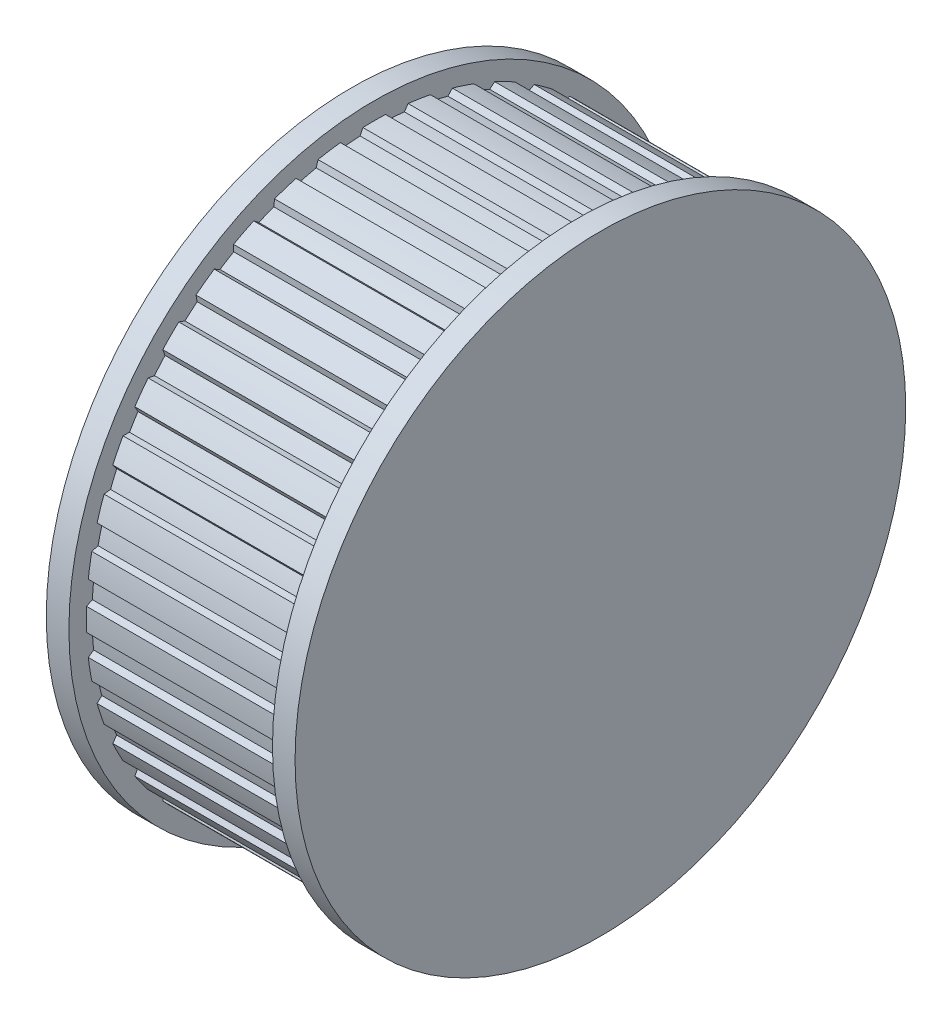
SolidWorks part; units mm, degrees
ref_plane "Front Plane" through (0, 0, 0) normal (0, 0, 1) x (1, 0, 0)
ref_plane "Top Plane" through (0, 0, 0) normal (0, 1, 0) x (1, 0, 0)
ref_plane "Right Plane" through (0, 0, 0) normal (1, 0, 0) x (0, 0, -1)
ref_plane "Plane4" through (0, 0, 0) normal (0, 0, -1) x (-1, 0, 0)
sketch "Sketch5" plane through (0, 0, 0) normal (1, 0, 0) x (0, 0, -1)
  line L1 (0, 12.73) -> (0, 0) construction
  line L2 (-0.6228, 12.4594) -> (-0.4998, 12.7202)
  line L3 (0.4998, 12.7202) -> (0.6228, 12.4594)
  line L4 (1.3339, 12.4035) -> (1.4963, 12.6418)
  line L5 (2.4835, 12.4854) -> (2.5642, 12.2086)
  line L6 (3.2578, 12.0421) -> (3.4554, 12.2521)
  line L7 (4.4061, 11.9432) -> (4.4425, 11.6572)
  line L8 (5.1015, 11.3842) -> (5.3295, 11.5607)
  line L9 (6.2201, 11.1069) -> (6.2114, 10.8187)
  line L10 (6.8196, 10.446) -> (7.0724, 10.5846)
  line L11 (7.8811, 9.9971) -> (7.8273, 9.7138)
  line L12 (8.3698, 9.2506) -> (8.6411, 9.3479)
  line L13 (9.3479, 8.6411) -> (9.2506, 8.3698)
  line L14 (9.7138, 7.8273) -> (9.9971, 7.8811)
  line L15 (10.5846, 7.0724) -> (10.446, 6.8196)
  line L16 (10.8187, 6.2114) -> (11.1069, 6.2201)
  line L17 (11.5607, 5.3295) -> (11.3842, 5.1015)
  line L18 (11.6572, 4.4425) -> (11.9432, 4.4061)
  line L19 (12.2521, 3.4554) -> (12.0421, 3.2578)
  line L20 (12.2086, 2.5642) -> (12.4854, 2.4835)
  line L21 (12.6418, 1.4963) -> (12.4035, 1.3339)
  line L22 (12.4594, 0.6228) -> (12.7202, 0.4998)
  line L23 (12.7202, -0.4998) -> (12.4594, -0.6228)
  line L24 (12.4035, -1.3339) -> (12.6418, -1.4963)
  line L25 (12.4854, -2.4835) -> (12.2086, -2.5642)
  line L26 (12.0421, -3.2578) -> (12.2521, -3.4554)
  line L27 (11.9432, -4.4061) -> (11.6572, -4.4425)
  line L28 (11.3842, -5.1015) -> (11.5607, -5.3295)
  line L29 (11.1069, -6.2201) -> (10.8187, -6.2114)
  line L30 (10.446, -6.8196) -> (10.5846, -7.0724)
  line L31 (9.9971, -7.8811) -> (9.7138, -7.8273)
  line L32 (9.2506, -8.3698) -> (9.3479, -8.6411)
  line L33 (8.6411, -9.3479) -> (8.3698, -9.2506)
  line L34 (7.8273, -9.7138) -> (7.8811, -9.9971)
  line L35 (7.0724, -10.5846) -> (6.8196, -10.446)
  line L36 (6.2114, -10.8187) -> (6.2201, -11.1069)
  line L37 (5.3295, -11.5607) -> (5.1015, -11.3842)
  line L38 (4.4425, -11.6572) -> (4.4061, -11.9432)
  line L39 (3.4554, -12.2521) -> (3.2578, -12.0421)
  line L40 (2.5642, -12.2086) -> (2.4835, -12.4854)
  line L41 (1.4963, -12.6418) -> (1.3339, -12.4035)
  line L42 (0.6228, -12.4594) -> (0.4998, -12.7202)
  line L43 (-0.4998, -12.7202) -> (-0.6228, -12.4594)
  line L44 (-1.3339, -12.4035) -> (-1.4963, -12.6418)
  line L45 (-2.4835, -12.4854) -> (-2.5642, -12.2086)
  line L46 (-3.2578, -12.0421) -> (-3.4554, -12.2521)
  line L47 (-4.4061, -11.9432) -> (-4.4425, -11.6572)
  line L48 (-5.1015, -11.3842) -> (-5.3295, -11.5607)
  line L49 (-6.2201, -11.1069) -> (-6.2114, -10.8187)
  line L50 (-6.8196, -10.446) -> (-7.0724, -10.5846)
  line L51 (-7.8811, -9.9971) -> (-7.8273, -9.7138)
  line L52 (-8.3698, -9.2506) -> (-8.6411, -9.3479)
  line L53 (-9.3479, -8.6411) -> (-9.2506, -8.3698)
  line L54 (-9.7138, -7.8273) -> (-9.9971, -7.8811)
  line L55 (-10.5846, -7.0724) -> (-10.446, -6.8196)
  line L56 (-10.8187, -6.2114) -> (-11.1069, -6.2201)
  line L57 (-11.5607, -5.3295) -> (-11.3842, -5.1015)
  line L58 (-11.6572, -4.4425) -> (-11.9432, -4.4061)
  line L59 (-12.2521, -3.4554) -> (-12.0421, -3.2578)
  line L60 (-12.2086, -2.5642) -> (-12.4854, -2.4835)
  line L61 (-12.6418, -1.4963) -> (-12.4035, -1.3339)
  line L62 (-12.4594, -0.6228) -> (-12.7202, -0.4998)
  line L63 (-12.7202, 0.4998) -> (-12.4594, 0.6228)
  line L64 (-12.4035, 1.3339) -> (-12.6418, 1.4963)
  line L65 (-12.4854, 2.4835) -> (-12.2086, 2.5642)
  line L66 (-12.0421, 3.2578) -> (-12.2521, 3.4554)
  line L67 (-11.9432, 4.4061) -> (-11.6572, 4.4425)
  line L68 (-11.3842, 5.1015) -> (-11.5607, 5.3295)
  line L69 (-11.1069, 6.2201) -> (-10.8187, 6.2114)
  line L70 (-10.446, 6.8196) -> (-10.5846, 7.0724)
  line L71 (-9.9971, 7.8811) -> (-9.7138, 7.8273)
  line L72 (-9.2506, 8.3698) -> (-9.3479, 8.6411)
  line L73 (-8.6411, 9.3479) -> (-8.3698, 9.2506)
  line L74 (-7.8273, 9.7138) -> (-7.8811, 9.9971)
  line L75 (-7.0724, 10.5846) -> (-6.8196, 10.446)
  line L76 (-6.2114, 10.8187) -> (-6.2201, 11.1069)
  line L77 (-5.3295, 11.5607) -> (-5.1015, 11.3842)
  line L78 (-4.4425, 11.6572) -> (-4.4061, 11.9432)
  line L79 (-3.4554, 12.2521) -> (-3.2578, 12.0421)
  line L80 (-2.5642, 12.2086) -> (-2.4835, 12.4854)
  line L81 (-1.4963, 12.6418) -> (-1.3339, 12.4035)
  arc A4 (1.3339, 12.4035) -> (0.6228, 12.4594) centre (0, 0) ccw
  arc A6 (0.4998, 12.7202) -> (-0.4998, 12.7202) centre (0, 0) ccw
  arc A7 (2.4835, 12.4854) -> (1.4963, 12.6418) centre (0, 0) ccw
  arc A8 (3.2578, 12.0421) -> (2.5642, 12.2086) centre (0, 0) ccw
  arc A9 (4.4061, 11.9432) -> (3.4554, 12.2521) centre (0, 0) ccw
  arc A10 (5.1015, 11.3842) -> (4.4425, 11.6572) centre (0, 0) ccw
  arc A11 (6.2201, 11.1069) -> (5.3295, 11.5607) centre (0, 0) ccw
  arc A12 (6.8196, 10.446) -> (6.2114, 10.8187) centre (0, 0) ccw
  arc A13 (7.8811, 9.9971) -> (7.0724, 10.5846) centre (0, 0) ccw
  arc A14 (8.3698, 9.2506) -> (7.8273, 9.7138) centre (0, 0) ccw
  arc A15 (9.3479, 8.6411) -> (8.6411, 9.3479) centre (0, 0) ccw
  arc A16 (9.7138, 7.8273) -> (9.2506, 8.3698) centre (0, 0) ccw
  arc A17 (10.5846, 7.0724) -> (9.9971, 7.8811) centre (0, 0) ccw
  arc A18 (10.8187, 6.2114) -> (10.446, 6.8196) centre (0, 0) ccw
  arc A19 (11.5607, 5.3295) -> (11.1069, 6.2201) centre (0, 0) ccw
  arc A20 (11.6572, 4.4425) -> (11.3842, 5.1015) centre (0, 0) ccw
  arc A21 (12.2521, 3.4554) -> (11.9432, 4.4061) centre (0, 0) ccw
  arc A22 (12.2086, 2.5642) -> (12.0421, 3.2578) centre (0, 0) ccw
  arc A23 (12.6418, 1.4963) -> (12.4854, 2.4835) centre (0, 0) ccw
  arc A24 (12.4594, 0.6228) -> (12.4035, 1.3339) centre (0, 0) ccw
  arc A25 (12.7202, -0.4998) -> (12.7202, 0.4998) centre (0, 0) ccw
  arc A26 (12.4035, -1.3339) -> (12.4594, -0.6228) centre (0, 0) ccw
  arc A27 (12.4854, -2.4835) -> (12.6418, -1.4963) centre (0, 0) ccw
  arc A28 (12.0421, -3.2578) -> (12.2086, -2.5642) centre (0, 0) ccw
  arc A29 (11.9432, -4.4061) -> (12.2521, -3.4554) centre (0, 0) ccw
  arc A30 (11.3842, -5.1015) -> (11.6572, -4.4425) centre (0, 0) ccw
  arc A31 (11.1069, -6.2201) -> (11.5607, -5.3295) centre (0, 0) ccw
  arc A32 (10.446, -6.8196) -> (10.8187, -6.2114) centre (0, 0) ccw
  arc A33 (9.9971, -7.8811) -> (10.5846, -7.0724) centre (0, 0) ccw
  arc A34 (9.2506, -8.3698) -> (9.7138, -7.8273) centre (0, 0) ccw
  arc A35 (8.6411, -9.3479) -> (9.3479, -8.6411) centre (0, 0) ccw
  arc A36 (7.8273, -9.7138) -> (8.3698, -9.2506) centre (0, 0) ccw
  arc A37 (7.0724, -10.5846) -> (7.8811, -9.9971) centre (0, 0) ccw
  arc A38 (6.2114, -10.8187) -> (6.8196, -10.446) centre (0, 0) ccw
  arc A39 (5.3295, -11.5607) -> (6.2201, -11.1069) centre (0, 0) ccw
  arc A40 (4.4425, -11.6572) -> (5.1015, -11.3842) centre (0, 0) ccw
  arc A41 (3.4554, -12.2521) -> (4.4061, -11.9432) centre (0, 0) ccw
  arc A42 (2.5642, -12.2086) -> (3.2578, -12.0421) centre (0, 0) ccw
  arc A43 (1.4963, -12.6418) -> (2.4835, -12.4854) centre (0, 0) ccw
  arc A44 (0.6228, -12.4594) -> (1.3339, -12.4035) centre (0, 0) ccw
  arc A45 (-0.4998, -12.7202) -> (0.4998, -12.7202) centre (0, 0) ccw
  arc A46 (-1.3339, -12.4035) -> (-0.6228, -12.4594) centre (0, 0) ccw
  arc A47 (-2.4835, -12.4854) -> (-1.4963, -12.6418) centre (0, 0) ccw
  arc A48 (-3.2578, -12.0421) -> (-2.5642, -12.2086) centre (0, 0) ccw
  arc A49 (-4.4061, -11.9432) -> (-3.4554, -12.2521) centre (0, 0) ccw
  arc A50 (-5.1015, -11.3842) -> (-4.4425, -11.6572) centre (0, 0) ccw
  arc A51 (-6.2201, -11.1069) -> (-5.3295, -11.5607) centre (0, 0) ccw
  arc A52 (-6.8196, -10.446) -> (-6.2114, -10.8187) centre (0, 0) ccw
  arc A53 (-7.8811, -9.9971) -> (-7.0724, -10.5846) centre (0, 0) ccw
  arc A54 (-8.3698, -9.2506) -> (-7.8273, -9.7138) centre (0, 0) ccw
  arc A55 (-9.3479, -8.6411) -> (-8.6411, -9.3479) centre (0, 0) ccw
  arc A56 (-9.7138, -7.8273) -> (-9.2506, -8.3698) centre (0, 0) ccw
  arc A57 (-10.5846, -7.0724) -> (-9.9971, -7.8811) centre (0, 0) ccw
  arc A58 (-10.8187, -6.2114) -> (-10.446, -6.8196) centre (0, 0) ccw
  arc A59 (-11.5607, -5.3295) -> (-11.1069, -6.2201) centre (0, 0) ccw
  arc A60 (-11.6572, -4.4425) -> (-11.3842, -5.1015) centre (0, 0) ccw
  arc A61 (-12.2521, -3.4554) -> (-11.9432, -4.4061) centre (0, 0) ccw
  arc A62 (-12.2086, -2.5642) -> (-12.0421, -3.2578) centre (0, 0) ccw
  arc A63 (-12.6418, -1.4963) -> (-12.4854, -2.4835) centre (0, 0) ccw
  arc A64 (-12.4594, -0.6228) -> (-12.4035, -1.3339) centre (0, 0) ccw
  arc A65 (-12.7202, 0.4998) -> (-12.7202, -0.4998) centre (0, 0) ccw
  arc A66 (-12.4035, 1.3339) -> (-12.4594, 0.6228) centre (0, 0) ccw
  arc A67 (-12.4854, 2.4835) -> (-12.6418, 1.4963) centre (0, 0) ccw
  arc A68 (-12.0421, 3.2578) -> (-12.2086, 2.5642) centre (0, 0) ccw
  arc A69 (-11.9432, 4.4061) -> (-12.2521, 3.4554) centre (0, 0) ccw
  arc A70 (-11.3842, 5.1015) -> (-11.6572, 4.4425) centre (0, 0) ccw
  arc A71 (-11.1069, 6.2201) -> (-11.5607, 5.3295) centre (0, 0) ccw
  arc A72 (-10.446, 6.8196) -> (-10.8187, 6.2114) centre (0, 0) ccw
  arc A73 (-9.9971, 7.8811) -> (-10.5846, 7.0724) centre (0, 0) ccw
  arc A74 (-9.2506, 8.3698) -> (-9.7138, 7.8273) centre (0, 0) ccw
  arc A75 (-8.6411, 9.3479) -> (-9.3479, 8.6411) centre (0, 0) ccw
  arc A76 (-7.8273, 9.7138) -> (-8.3698, 9.2506) centre (0, 0) ccw
  arc A77 (-7.0724, 10.5846) -> (-7.8811, 9.9971) centre (0, 0) ccw
  arc A78 (-6.2114, 10.8187) -> (-6.8196, 10.446) centre (0, 0) ccw
  arc A79 (-5.3295, 11.5607) -> (-6.2201, 11.1069) centre (0, 0) ccw
  arc A80 (-4.4425, 11.6572) -> (-5.1015, 11.3842) centre (0, 0) ccw
  arc A81 (-3.4554, 12.2521) -> (-4.4061, 11.9432) centre (0, 0) ccw
  arc A82 (-2.5642, 12.2086) -> (-3.2578, 12.0421) centre (0, 0) ccw
  arc A83 (-1.4963, 12.6418) -> (-2.4835, 12.4854) centre (0, 0) ccw
  arc A84 (-0.6228, 12.4594) -> (-1.3339, 12.4035) centre (0, 0) ccw
  point P204 (0, 0)
  dimension "D2" = 12.73
  dimension "D4" = 12.475
  dimension "D3" = 0.4998
  dimension "D5" = 0.6228
  dimension "D1" = 40
extrude "Boss-Extrude1" add sketch "Sketch5" along normal blind 9
sketch "Sketch6" plane through (9, 0, 0) normal (1, 0, 0) x (0, 0, -1)
  circle A0 centre (0, 0) radius 13.5
  dimension "D1" = 27
extrude "Boss-Extrude2" add sketch "Sketch6" along normal blind 1
extrude "Boss-Extrude3" add sketch "Sketch6<3>" against normal blind 1 from surface starting at face at (0, 0, 0)
sketch "Sketch6<3>" plane through (9, 0, 0) normal (1, 0, 0) x (0, 0, -1) same geometry as "Sketch6"
sketch "Sketch7" plane through (-1, 0, 0) normal (-1, 0, 0) x (0, 0, 1)
  circle A0 centre (0, 0) radius 5
  dimension "D1" = 10
extrude "Boss-Extrude4" add sketch "Sketch7" along normal blind 6
ref_plane "Plane5" through (0, 5, 0) normal (0, 1, 0) x (1, 0, 0)
ref_plane "Plane6" through (0, 0, 5) normal (0, 0, 1) x (1, 0, 0)
sketch "Sketch8" plane through (-7, 0, 0) normal (-1, 0, 0) x (0, 0, 1)
  circle A0 centre (0, 0) radius 2
  dimension "D1" = 4
extrude "Cut-Extrude1" cut sketch "Sketch8" against normal blind 6
sketch "Sketch9" plane through (0, 5, 0) normal (0, 1, 0) x (1, 0, 0)
  line L0 (-4, 5) -> (-4, 0) construction
  line L1 (-1, 5) -> (-7, 5) construction
  line L2 (0, 0) -> (-4, 0) construction
  circle A0 centre (-4, 0) radius 1.6
  dimension "D1" = 3.2
extrude "Cut-Extrude2" cut sketch "Sketch9" against normal up to next
